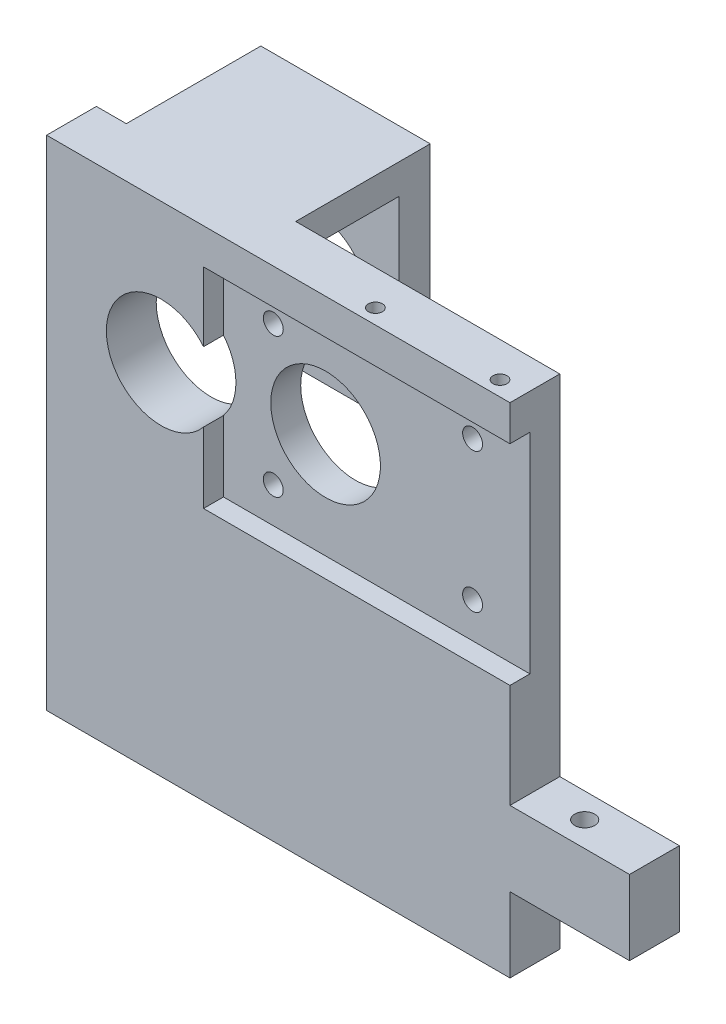
SolidWorks part; units mm, degrees
material "ABS"
ref_plane "Front Plane" through (0, 0, 0) normal (0, 0, 1) x (1, 0, 0)
ref_plane "Top Plane" through (0, 0, 0) normal (0, 1, 0) x (1, 0, 0)
ref_plane "Right Plane" through (0, 0, 0) normal (1, 0, 0) x (0, 0, -1)
sketch "Sketch1" plane through (0, 0, 0) normal (0, 0, 1) x (1, 0, 0)
  line L1 (-76.1871, 64.9281) -> (16.8129, 64.9281)
  line L2 (-76.1871, 64.9281) -> (-76.1871, -35.0719)
  line L3 (-76.1871, -35.0719) -> (16.8129, -35.0719)
  line L4 (16.8129, 64.9281) -> (16.8129, -35.0719)
  dimension "D1" = 93
  dimension "D2" = 100
extrude "Boss-Extrude2" add sketch "Sketch1" along normal blind 10 contours L1 L4 L3 L2
sketch "Sketch3" plane through (0, 0, 0) normal (0, 0, -1) x (-1, 0, 0)
  line L0 (76.1871, -35.0719) -> (-16.8129, -35.0719) construction
  line L1 (-16.8129, 64.9281) -> (-6.8129, 64.9281)
  line L2 (-16.8129, 64.9281) -> (-16.8129, -35.0719)
  line L3 (-16.8129, -35.0719) -> (-6.8129, -35.0719)
  line L4 (-6.8129, 64.9281) -> (-6.8129, -35.0719)
  line L5 (-16.8129, 64.9281) -> (-16.8129, -35.0719) construction
  dimension "D1" = 0
  dimension "D2" = 0
  dimension "D3" = 10
  dimension "D4" = 100
sketch "Sketch4" plane through (16.8129, 0, 0) normal (1, 0, 0) x (0, 0, -1)
  line L0 (-10, 64.9281) -> (-10, -35.0719) construction
  line L1 (-10, -5.0719) -> (0.01, -5.0719)
  line L2 (-10, -5.0719) -> (-10, -20.0719)
  line L3 (-10, -20.0719) -> (0.01, -20.0719)
  line L4 (0.01, -5.0719) -> (0.01, -20.0719)
  line L6 (-10, -35.0719) -> (0, -35.0719) construction
  dimension "D1" = 15
  dimension "D2" = 15
extrude "Boss-Extrude4" add sketch "Sketch4" along normal blind 24
sketch "Sketch5" plane through (0, -5.0719, 0) normal (0, 1, 0) x (1, 0, 0)
  line L0 (40.8129, -10) -> (16.8129, -10) construction
  line L2 (16.8129, 0) -> (16.8129, -10) construction
  circle A0 centre (26.8129, -5) radius 2
  dimension "D2" = 4
  dimension "D3" = 10
  dimension "D1" = 5
extrude "Cut-Extrude1" cut sketch "Sketch5" against normal blind 50
sketch "Sketch6" plane through (0, 0, 10) normal (0, 0, -1) x (-1, 0, 0)
  line L2 (76.1871, -35.0719) -> (-16.8129, -35.0719) construction
  line L3 (-16.8129, 64.9281) -> (-16.8129, -35.0719) construction
  circle A0 centre (-1.8129, -24.5719) radius 7.5
  dimension "D1" = 15
  dimension "D2" = 10.5
  dimension "D3" = 15
sketch "Sketch7" plane through (0, 0, 0) normal (0, 0, -1) x (-1, 0, 0)
  circle A0 centre (24.1871, 36.9281) radius 11
  circle A1 centre (24.1871, 36.9281) radius 9.3 construction
  dimension "D1" = 22
extrude "Cut-Extrude3" cut sketch "Sketch7" against normal blind 50
sketch "Sketch14" plane through (0, 0, 10) normal (0, 0, 1) x (1, 0, 0)
  line L0 (16.8129, 64.9281) -> (16.8129, -5.0719) construction
  line L1 (-44.6871, 15.7891) -> (16.8129, 15.7891)
  line L2 (-44.6871, 15.7891) -> (-44.6871, 57.7891)
  line L3 (-44.6871, 57.7891) -> (16.8129, 57.7891)
  line L4 (16.8129, 15.7891) -> (16.8129, 57.7891)
  dimension "D1" = 42
  dimension "D3" = 61.5
extrude "Cut-Extrude8" cut sketch "Sketch14" against normal blind 4
sketch "Sketch15" plane through (0, 0, 0) normal (0, 0, -1) x (-1, 0, 0)
  circle A0 centre (24.1871, 36.9281) radius 10
  circle A1 centre (24.1871, 36.9281) radius 11 construction
  dimension "D1" = 20
  dimension "D2" = 0
sketch "Sketch16" plane through (0, 0, 10) normal (0, 0, 1) x (1, 0, 0)
  line L0 (-43.6871, 56.9281) -> (14.3129, 56.9281) construction
  line L1 (-44.1871, 57.3281) -> (16.8129, 57.3281)
  line L2 (-44.1871, 57.3281) -> (-44.1871, 64.9281)
  line L3 (-44.1871, 64.9281) -> (16.8129, 64.9281)
  line L4 (16.8129, 57.3281) -> (16.8129, 64.9281)
  dimension "D1" = 0.4
sketch "Sketch17" plane through (0, 0, 10) normal (0, 0, 1) x (1, 0, 0)
  line L0 (16.8129, 15.7891) -> (16.8129, -5.0719) construction
  line L1 (-44.1871, 16.7281) -> (16.8129, 16.7281)
  line L2 (-44.1871, 16.7281) -> (-44.1871, -20.0719)
  line L3 (-44.1871, -20.0719) -> (16.8129, -20.0719)
  line L4 (16.8129, 16.7281) -> (16.8129, -20.0719)
  line L5 (-43.6871, 16.9281) -> (14.3129, 16.9281) construction
  line L6 (40.8129, -20.0719) -> (16.8129, -20.0719) construction
  line L9 (16.8129, -20.0719) -> (40.8129, -20.0719)
  line L10 (16.8129, -20.0719) -> (16.8129, -5.0719)
  line L11 (16.8129, -5.0719) -> (40.8129, -5.0719)
  line L12 (40.8129, -20.0719) -> (40.8129, -5.0719)
  line L13 (16.8129, -20.0719) -> (40.8129, -5.0719) construction
  line L14 (16.8129, -5.0719) -> (40.8129, -20.0719) construction
  point P16 (28.8129, -12.5719)
  dimension "D1" = 0.2
  dimension "D2" = 0
sketch "Sketch19" plane through (0, 0, 0) normal (0, 0, -1) x (-1, 0, 0)
  line L1 (-16.8129, 64.9281) -> (-16.8129, -35.0719) construction
  circle A0 centre (53.1871, 36.9281) radius 11
  circle A1 centre (24.1871, 36.9281) radius 10 construction
  dimension "D1" = 22
  dimension "D3" = 0
  dimension "D2" = 70
extrude "Cut-Extrude11" cut sketch "Sketch19" against normal blind 15
sketch "Sketch20" plane through (0, 0, 6) normal (0, 0, 1) x (1, 0, 0)
  circle A0 centre (-34.6871, 50.9281) radius 2
  circle A1 centre (5.3129, 50.9281) radius 2
  circle A2 centre (-34.6871, 22.9281) radius 2
  circle A3 centre (5.3129, 22.9281) radius 2
  arc A5 (-27.0471, 34.1316) -> (-27.0471, 39.7246) centre (-24.1871, 36.9281) ccw construction
  circle A6 centre (-24.1871, 36.9281) radius 11 construction
  dimension "D1" = 4
  dimension "D2" = 4
  dimension "D3" = 4
  dimension "D4" = 4
  dimension "D5" = 0
  dimension "D6" = 28
  dimension "D7" = 0
  dimension "D8" = 40
  dimension "D9" = 14
  dimension "D10" = 10.5
  dimension "D11" = 28
  dimension "D12" = 40
extrude "Cut-Extrude12" cut sketch "Sketch20" against normal blind 10
sketch "Sketch8" plane through (0, 64.9281, 0) normal (0, 1, 0) x (1, 0, 0)
  line L0 (-76.1871, -10) -> (16.8129, -10) construction
  line L5 (16.8129, 0) -> (12.3014, -10) construction
  line L6 (16.8129, -10) -> (7.8859, 0) construction
  line L8 (16.8129, -10) -> (16.8129, 0) construction
  line L9 (-76.1871, 0) -> (16.8129, 0) construction
  circle A0 centre (11.8129, -7) radius 1.4
  circle A1 centre (-13.1871, -7) radius 1.4
  point P4 (13.816, -6.6429)
  dimension "D1" = 25
  dimension "D2" = 5
  dimension "D3" = 2.8
  dimension "D4" = 7
  dimension "D5" = 7
extrude "Cut-Extrude4" cut sketch "Sketch8" against normal blind 5.5 contours A1 | A0 region at (-13.1871, 64.9281, 7)
sketch "Sketch21" plane through (0, 0, 0) normal (0, 0, -1) x (-1, 0, 0)
  line L1 (76.1871, 64.9281) -> (36.1871, 64.9281)
  line L2 (76.1871, 64.9281) -> (76.1871, 58.9281)
  line L3 (76.1871, 58.9281) -> (36.1871, 58.9281)
  line L4 (36.1871, 64.9281) -> (36.1871, 58.9281)
  dimension "D1" = 6
  dimension "D2" = 40
extrude "Boss-Extrude5" add sketch "Sketch21" along normal blind 27
sketch "Sketch22" plane through (0, 58.9281, 0) normal (0, -1, 0) x (1, 0, 0)
  line L0 (-76.1871, -27) -> (-76.1871, 0) construction
  line L1 (-36.1871, -27) -> (-76.1871, -27)
  line L2 (-36.1871, -27) -> (-36.1871, -20.7)
  line L3 (-36.1871, -20.7) -> (-76.1871, -20.7)
  line L4 (-76.1871, -27) -> (-76.1871, -20.7)
  dimension "D1" = 6.3
extrude "Boss-Extrude7" add sketch "Sketch22" along normal blind 40
extrude "Cut-Extrude14" cut sketch "Sketch19<3>" along normal blind 40
sketch "Sketch19<3>" plane through (0, 0, 0) normal (0, 0, -1) x (-1, 0, 0) same geometry as "Sketch19"
sketch "Sketch24" plane through (0, 0, -27) normal (0, 0, -1) x (-1, 0, 0)
  line L0 (76.1871, 64.9281) -> (36.1871, 64.9281) construction
  line L1 (76.1871, 18.9281) -> (70.1871, 18.9281)
  line L2 (76.1871, 18.9281) -> (76.1871, 64.9281)
  line L3 (76.1871, 64.9281) -> (70.1871, 64.9281)
  line L4 (70.1871, 18.9281) -> (70.1871, 64.9281)
  circle A0 centre (53.1871, 36.9281) radius 11 construction
  dimension "D1" = 17
extrude "Cut-Extrude15" cut sketch "Sketch24" against normal blind 27
